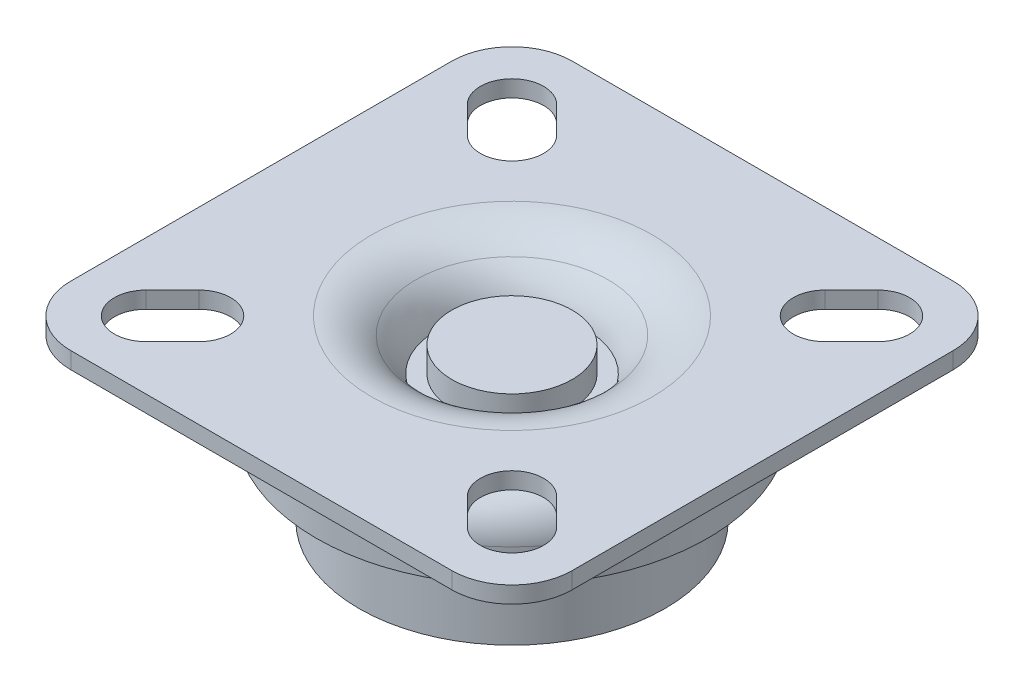
SolidWorks part; units mm, degrees
material "Galvanized Steel"
ref_plane "Front Plane" through (0, 0, 0) normal (0, 0, 1) x (1, 0, 0)
ref_plane "Top Plane" through (0, 0, 0) normal (0, 1, 0) x (1, 0, 0)
ref_plane "Right Plane" through (0, 0, 0) normal (1, 0, 0) x (0, 0, -1)
sketch "Sketch1" plane through (0, 0, 0) normal (0, 1, 0) x (1, 0, 0)
  line L1 (-25, -25) -> (25, -25)
  line L2 (-25, -25) -> (-25, 25)
  line L3 (-25, 25) -> (25, 25)
  line L4 (25, -25) -> (25, 25)
  line L5 (-25, -25) -> (25, 25) construction
  line L6 (-25, 25) -> (25, -25) construction
  point P0 (0, 0)
  dimension "D1" = 50
extrude "boss_plate" add sketch "Sketch1" along normal blind 1.66
fillet "fillet plate corners" radius 6 4 edges at (25, 0.83, 25) (-25, 0.83, -25) (25, 0.83, -25) (-25, 0.83, 25)
sketch "Sketch2" plane through (0, 1.66, 0) normal (0, 1, 0) x (1, 0, 0)
  line L0 (15.6, 15.6) -> (18.25, 18.25) construction
  line L1 (-15.6, -15.6) -> (15.6, -15.6) construction
  line L2 (-15.6, -15.6) -> (-15.6, 15.6) construction
  line L3 (-15.6, 15.6) -> (15.6, 15.6) construction
  line L4 (15.6, -15.6) -> (15.6, 15.6) construction
  line L5 (-15.6, -15.6) -> (15.6, 15.6) construction
  line L6 (-15.6, 15.6) -> (15.6, -15.6) construction
  line L7 (-18.25, -18.25) -> (18.25, -18.25) construction
  line L8 (-18.25, -18.25) -> (-18.25, 18.25) construction
  line L9 (-18.25, 18.25) -> (18.25, 18.25) construction
  line L10 (18.25, -18.25) -> (18.25, 18.25) construction
  line L11 (-18.25, -18.25) -> (18.25, 18.25) construction
  line L12 (-18.25, 18.25) -> (18.25, -18.25) construction
  line L13 (13.3726, 17.8274) -> (16.0226, 20.4774)
  line L14 (17.8274, 13.3726) -> (20.4774, 16.0226)
  arc A0 (13.3726, 17.8274) -> (17.8274, 13.3726) centre (15.6, 15.6) ccw
  arc A1 (20.4774, 16.0226) -> (16.0226, 20.4774) centre (18.25, 18.25) ccw
  point P0 (0, 0)
  point P6 (0, 0)
  point P11 (16.925, 16.925)
  dimension "D1" = 36.5
  dimension "D2" = 31.2
  dimension "D3" = 6.3
extrude "cut slot" cut sketch "Sketch2" against normal through all
ref_axis "CENTER" through (0, -2.1474, 0) along (0, 1, 0)
pattern_circular "slot pattern" count 4 over 360 about axis through (0, -2.1474, 0) along (0, 1, 0) of "cut slot"
sketch "Sketch3" plane through (0, 0, 0) normal (0, 0, 1) x (1, 0, 0)
  line L0 (19.51, -7.8) -> (19.51, 0)
  line L1 (0, 0) -> (19.51, 0)
  line L2 (-19, 0) -> (19, 0) construction
  line L3 (0, -2.1474) -> (0, 12.1143) construction
  line L4 (0, 0) -> (0, -13.4127) construction
  line L5 (15.25, -16) -> (15.25, -7.8)
  line L6 (15.25, -7.8) -> (19.51, -7.8)
  line L7 (15.25, -16) -> (13.85, -16)
  line L8 (0, -10.7) -> (4.5, -10.7)
  line L9 (0, 0) -> (0, -10.7)
  arc A0 (4.5, -10.7) -> (13.85, -16) centre (4.5, -21.5974) cw
  dimension "D1" = 7.8
  dimension "D2" = 39.02
  dimension "D3" = 16
  dimension "D4" = 16
  dimension "D5" = 30.5
  dimension "D6" = 5.3
  dimension "D7" = 9
  dimension "D8" = 1.4
revolve "bearing_upper_seat" add sketch "Sketch3" angle 360 about L4
sketch "Sketch4" plane through (0, 0, 0) normal (0, 0, 1) x (1, 0, 0)
  line L0 (-6, -3.34) -> (-6, -0.84)
  line L1 (-19, 1.66) -> (19, 1.66) construction
  line L2 (-14, 1.66) -> (0, 1.66)
  line L3 (0, 1.66) -> (0, -20.7853) construction
  line L4 (0, -2.1474) -> (0, 12.1143) construction
  line L5 (-6, -0.84) -> (0, -0.84)
  line L6 (0, -0.84) -> (0, 1.66)
  line L8 (-6, -3.34) -> (-7.5, -3.34)
  arc A0 (-14, 1.66) -> (-7.5, -3.34) centre (-14, -5.065) cw
  dimension "D1" = 28
  dimension "D2" = 2.5
  dimension "D3" = 5
  dimension "D4" = 12
  dimension "D5" = 1.5
revolve "cut_plate_forming" cut sketch "Sketch4" angle 360 about L3
fillet "Fillet2" radius 4.5 1 edges at (0, 0, 19.51)
ref_axis "Axis1" through (18.25, 0, -18.25) along (0, 1, 0)
ref_axis "Axis2" through (18.25, 0, 18.25) along (0, 1, 0)
ref_axis "Axis3" through (-18.25, 0, 18.25) along (0, 1, 0)
ref_axis "Axis4" through (-18.25, 0, -18.25) along (0, 1, 0)
